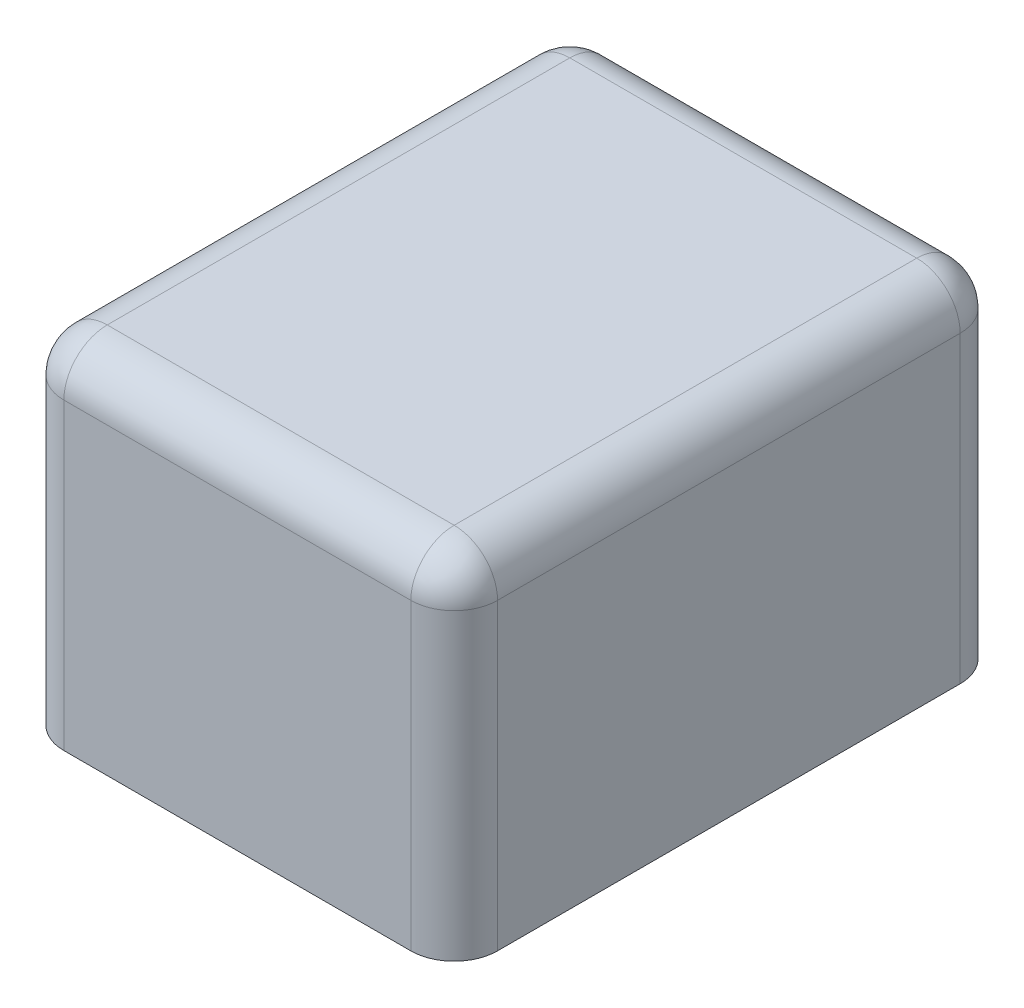
SolidWorks part; units mm, degrees
ref_plane "Front Plane" through (0, 0, 0) normal (0, 0, 1) x (1, 0, 0)
ref_plane "Top Plane" through (0, 0, 0) normal (0, 1, 0) x (1, 0, 0)
ref_plane "Right Plane" through (0, 0, 0) normal (1, 0, 0) x (0, 0, -1)
sketch "Sketch2" plane through (0, 0, 0) normal (0, 1, 0) x (1, 0, 0)
  line L1 (0, 0) -> (15, 0)
  line L2 (0, 0) -> (0, 19)
  line L3 (0, 19) -> (15, 19)
  line L4 (15, 0) -> (15, 19)
  dimension "D1" = 15
  dimension "D2" = 19
extrude "Boss-Extrude1" add sketch "Sketch2" along normal blind 10
sketch "Sketch3" plane through (0, 10, 0) normal (0, 1, 0) x (1, 0, 0)
  line L1 (0, 19) -> (15, 19)
  line L2 (0, 19) -> (0, 0)
  line L3 (0, 0) -> (15, 0)
  line L4 (15, 19) -> (15, 0)
extrude "Boss-Extrude2" add sketch "Sketch3" along normal blind 2
fillet "Fillet1" radius 1.5 4 edges at (7.5, 12, -19) (15, 12, -9.5) (7.5, 12, 0) (0, 12, -9.5)
fillet "Fillet3" radius 1.5 8 edges at (14.5607, 11.5607, -18.5607) (14.5607, 11.5607, -0.4393) (0.4393, 11.5607, -0.4393) (0.4393, 11.5607, -18.5607) (15, 5.25, -19) (15, 5.25, 0) (0, 5.25, 0) (0, 5.25, -19)
